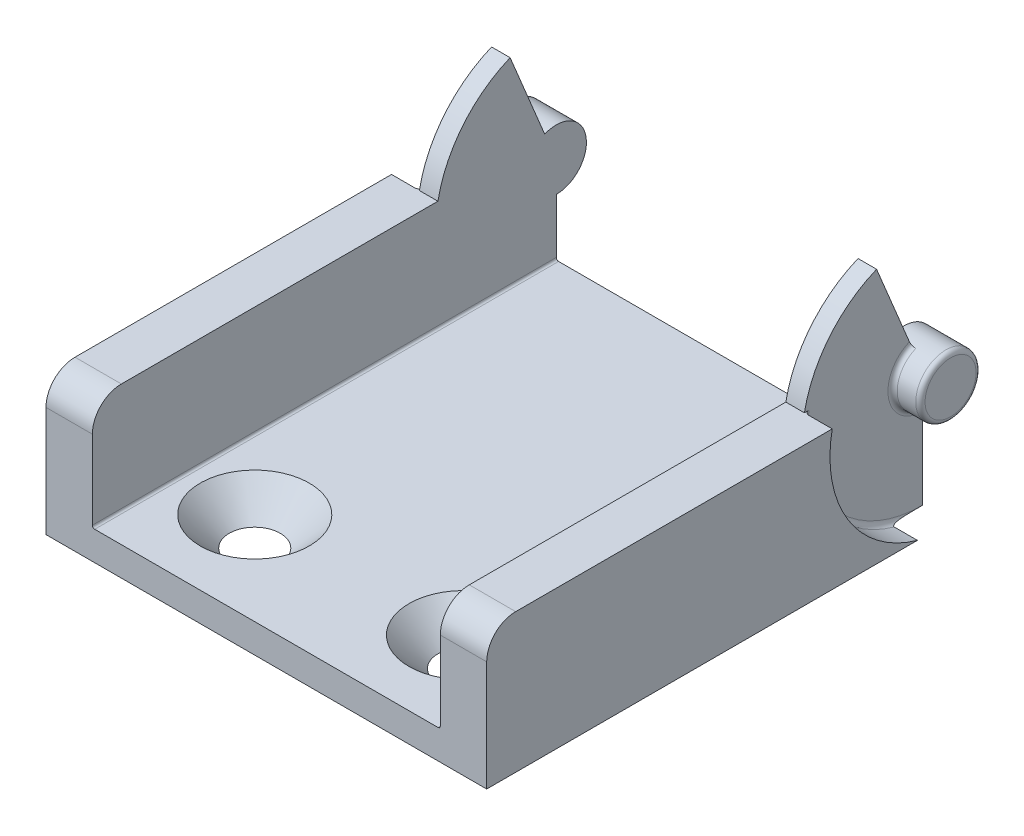
SolidWorks part; units mm, degrees
ref_plane "Front Plane" through (0, 0, 0) normal (0, 0, 1) x (1, 0, 0)
ref_plane "Top Plane" through (0, 0, 0) normal (0, 1, 0) x (1, 0, 0)
ref_plane "Right Plane" through (0, 0, 0) normal (1, 0, 0) x (0, 0, -1)
sketch "Sketch8" plane through (0, 0, 0) normal (1, 0, 0) x (0, 0, -1)
  line L0 (0, 2) -> (0, -10)
  line L1 (0, -10) -> (40, -10)
  line L2 (40, -10) -> (40, 0)
  line L3 (40, 0) -> (36.0201, 9.6083)
  line L6 (29.7941, 2) -> (0, 2)
  arc A0 (36.0201, 9.6083) -> (29.7941, 2) centre (40, 0) ccw
  dimension "D6" = 20.8
  dimension "D1" = 40
  dimension "D2" = 12
  dimension "D3" = 10
  dimension "D4" = 10
  dimension "D5" = 22.5
extrude "Boss-Extrude5" add sketch "Sketch8" along normal mid plane 38
sketch "Sketch4" plane through (19, 0, 0) normal (1, 0, 0) x (0, 0, -1)
  line L1 (32.6461, 7.3539) -> (50.4, 25.1078)
  line L2 (50.4, 25.1078) -> (50.4, 0)
  arc A0 (32.6461, 7.3539) -> (50.4, 0) centre (40, 0) ccw
  dimension "D2" = 20.8
  dimension "D1" = 45
extrude "Cut-Extrude1" cut sketch "Sketch4" against normal blind 2.4
mirror "Mirror1" about plane through (0, 0, 0) normal (1, 0, 0) of "Cut-Extrude1"
sketch "Sketch5" plane through (0, 0, 0) normal (1, 0, 0) x (0, 0, -1)
  circle A0 centre (40, 0) radius 2.6
  dimension "D1" = 5.2
extrude "Boss-Extrude4" add sketch "Sketch5" along normal up to surface and the other way up to surface up to face at (19, -4.3579, -16.15) other way up to face at (-19, -4.3579, -16.15)
sketch "Sketch7" plane through (0, 0, 0) normal (0, 0, 1) x (1, 0, 0)
  line L1 (-14.8, -7.5) -> (14.8, -7.5)
  line L2 (-15, -7.3) -> (-15, 12.3)
  line L3 (-14.8, 12.5) -> (14.8, 12.5)
  line L4 (15, -7.3) -> (15, 12.3)
  arc A0 (-15, 12.3) -> (-14.8, 12.5) centre (-14.8, 12.3) cw
  arc A1 (-14.8, -7.5) -> (-15, -7.3) centre (-14.8, -7.3) cw
  arc A2 (14.8, -7.5) -> (15, -7.3) centre (14.8, -7.3) ccw
  arc A3 (14.8, 12.5) -> (15, 12.3) centre (14.8, 12.3) cw
  point P0 (0, 0)
  point P1 (0, -7.5)
  dimension "D3" = 0.2
  dimension "D1" = 7.5
  dimension "D2" = 20
  dimension "D4" = 30
extrude "Cut-Extrude3" cut sketch "Sketch7" against normal through all and the other way through all
fillet "Fillet17" radius 0.4 6 edges at (-19, 0, -42.6) (19, 0, -42.6) (-16.6, -0.5072, -37.45) (16.6, -0.5072, -37.45) (16.6, -5.4317, -31.1311) (-16.6, -5.4317, -31.1311)
fillet "Скругление1" radius 2.5 2 edges at (17, 2, 0) (-17, 2, 0)
hole_wizard "Зенковка для винта с полупотайной головкой M41" positions "Трехмерный эскиз1" profile "Эскиз1" countersink size "M4" standard "ISO"
sketch3d "Трехмерный эскиз1"
  line L0 (-9, -7.5, -8) -> (9, -7.5, -8) construction
  line L2 (14.8, -7.5, 0) -> (-14.8, -7.5, 0) construction
  point P0 (-9, -7.5, -8)
  point P2 (9, -7.5, -8)
  point P12 (0, -7.5, -8)
  point P13 (0, -7.5, 0)
  dimension "D1" = 18
  dimension "D2" = 8
sketch "Эскиз1" plane through (-9, -7.5, -8) normal (1, 0, 0) x (0, 0, 1)
  line L0 (0, 0) -> (0, 9.7618)
  line L1 (0, 9.7618) -> (2.1, 8.5)
  line L2 (2.1, 8.5) -> (2.1, 2.6)
  line L3 (2.1, 2.6) -> (4.7, 0)
  line L5 (4.7, 0) -> (0, 0)
  line L6 (-2.1, 2.6) -> (-4.7, 0) construction
  line L10 (0, 9.7618) -> (-2.1, 8.5) construction
  line L11 (0, -6.35) -> (0, 107.95) construction
  dimension "Диаметр отверстия" = 4.2
  dimension "Глубина отверстия" = 8.5
  dimension "Диаметр передней зенковки" = 9.4
  dimension "Угол передней зенковки" = 90
  dimension "Угол заточки сверла" = 118
equation "\"W\" = 30"
equation "\"D1@Boss-Extrude5\"=\"W\"+3.20мм + 4.8мм"
equation "\"D4@Sketch7\"=\"W\""
equation "\"D1@Трехмерный эскиз1\"=\"W\"-12"
